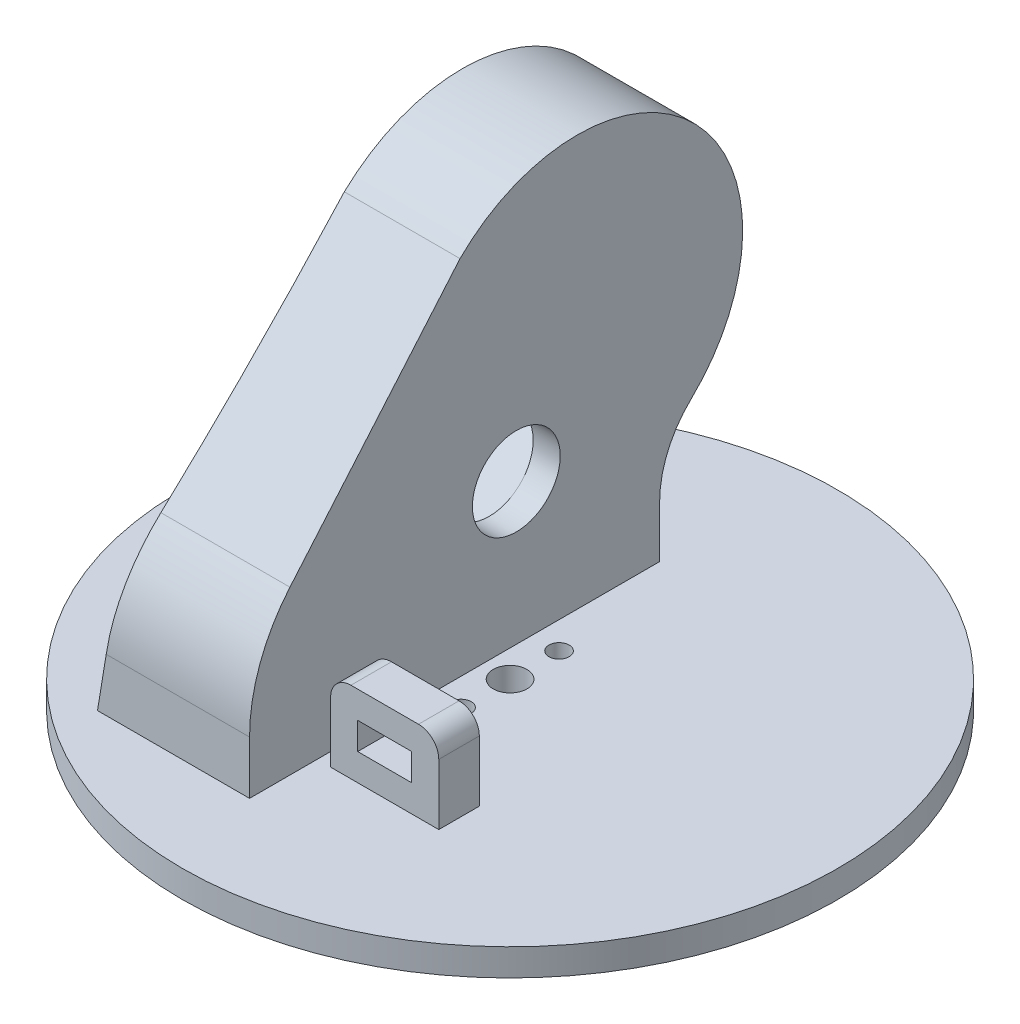
SolidWorks part; units mm, degrees
ref_plane "Front Plane" through (0, 0, 0) normal (0, 0, 1) x (1, 0, 0)
ref_plane "Top Plane" through (0, 0, 0) normal (0, 1, 0) x (1, 0, 0)
ref_plane "Right Plane" through (0, 0, 0) normal (1, 0, 0) x (0, 0, -1)
sketch "Sketch2" plane through (0, 0, 0) normal (0, 1, 0) x (1, 0, 0)
  circle A0 centre (0, 0) radius 48.5
  dimension "D1" = 97
extrude "Boss-Extrude1" add sketch "Sketch2" along normal blind 4
sketch "Sketch4" plane through (0, 0, 0) normal (0, -1, 0) x (1, 0, 0)
  circle A0 centre (0, 7.25) radius 1.5
  circle A1 centre (0, -7.25) radius 1.5
  dimension "D1" = 3
  dimension "D2" = 3
  dimension "D3" = 14.5
  dimension "D4" = 7.25
extrude "Cut-Extrude2" cut sketch "Sketch4" against normal through all
sketch "Sketch5" plane through (0, 0, 0) normal (0, -1, 0) x (1, 0, 0)
  circle A0 centre (0, 0) radius 2.5
  dimension "D1" = 5
extrude "Cut-Extrude3" cut sketch "Sketch5" against normal through all
ref_plane "Plane1" through (-4, 0, 0) normal (1, 0, 0) x (0, 0, -1)
sketch "Sketch7" plane through (-4, 0, 0) normal (1, 0, 0) x (0, 0, -1)
  line L0 (23.1299, 11.6445) -> (23.1299, 4)
  line L5 (48.5, 4) -> (-48.5, 4) construction
  line L6 (-27.2273, 29.5362) -> (-1.2843, 55.4793)
  line L7 (-43.5609, 4) -> (23.1299, 4)
  line L11 (-34.5496, 4) -> (-34.5496, 11.8586)
  arc A4 (28.7298, 24.692) -> (-1.2843, 55.4793) centre (13.9185, 40.2765) ccw
  arc A5 (28.7298, 24.692) -> (23.1299, 11.6445) centre (41.1299, 11.6445) ccw
  arc A6 (-27.2273, 29.5362) -> (-34.5496, 11.8586) centre (-9.5496, 11.8586) ccw
  dimension "D1" = 25
  dimension "D4" = 43
  dimension "D3" = 18
  dimension "D5" = 45
extrude "Boss-Extrude2" add sketch "Sketch7" against normal blind 14 contours A5 A4 L6 L7 L0 | A4 | A4 | A4 | L6 A6 L7 region at (-4, 29.3392, -2.7362)
ref_plane "Plane2" through (-6, 0, 0) normal (1, 0, 0) x (0, 0, -1)
sketch "Sketch17" plane through (-18, 0, 0) normal (-1, 0, 0) x (0, 0, 1)
  line L0 (29.3486, 31.6576) -> (3.4056, 57.6006)
  line L1 (-26.1299, 11.6445) -> (-26.1299, 1)
  line L2 (-26.1299, 1) -> (37.5496, 1)
  line L3 (37.5496, 1) -> (37.5496, 11.8586)
  line L4 (27.2273, 29.5362) -> (1.2843, 55.4793)
  line L5 (-23.1299, 11.6445) -> (-23.1299, 4)
  line L6 (-23.1299, 4) -> (34.5496, 4)
  line L7 (34.5496, 4) -> (34.5496, 11.8586)
  line L9 (-23.1299, 11.6445) -> (-23.1299, 4)
  line L10 (-23.1299, 4) -> (34.5496, 4)
  line L11 (34.5496, 4) -> (34.5496, 11.8586)
  line L12 (-26.1299, 4) -> (37.5496, 4)
  line L13 (48.5, 4) -> (-48.5, 4) construction
  line L14 (3.4056, 57.6006) -> (28.5745, 28.0776)
  line L15 (1.2843, 55.4793) -> (26.295, 26.1272)
  line L16 (31.5496, 11.8586) -> (31.5496, 4)
  line L18 (27.2273, 29.5362) -> (1.2843, 55.4793) construction
  arc A0 (3.4056, 57.6006) -> (-30.7965, 22.5174) centre (-13.9185, 40.2765) ccw
  arc A1 (-26.1299, 11.6445) -> (-30.7965, 22.5174) centre (-41.1299, 11.6445) ccw
  arc A2 (37.5496, 11.8586) -> (29.3486, 31.6576) centre (9.5496, 11.8586) ccw
  arc A3 (1.2843, 55.4793) -> (-28.7298, 24.692) centre (-13.9185, 40.2765) ccw
  arc A4 (-23.1299, 11.6445) -> (-28.7298, 24.692) centre (-41.1299, 11.6445) ccw
  arc A5 (34.5496, 11.8586) -> (27.2273, 29.5362) centre (9.5496, 11.8586) ccw
  arc A6 (1.2843, 55.4793) -> (-28.7298, 24.692) centre (-13.9185, 40.2765) ccw
  arc A7 (-23.1299, 11.6445) -> (-28.7298, 24.692) centre (-41.1299, 11.6445) ccw
  arc A8 (34.5496, 11.8586) -> (27.2273, 29.5362) centre (9.5496, 11.8586) ccw
  arc A9 (31.5496, 11.8586) -> (25.106, 27.4149) centre (9.5496, 11.8586) ccw
  line M16 (27.2273, 29.5362) -> (1.2843, 55.4793)
  arc M17 (1.2843, 55.4793) -> (-28.7298, 24.692) centre (-13.9185, 40.2765) ccw
  arc M18 (-28.7298, 24.692) -> (-23.1299, 11.6445) centre (-41.1299, 11.6445) cw
  line M19 (-23.1299, 11.6445) -> (-23.1299, 4)
  line M21 (34.5496, 4) -> (34.5496, 11.8586)
  arc M22 (34.5496, 11.8586) -> (27.2273, 29.5362) centre (9.5496, 11.8586) ccw
  dimension "D1" = 0
  dimension "D2" = 3
  dimension "D3" = 3
extrude "Boss-Extrude7" add sketch "Sketch17" along normal blind 9 and the other way up to surface (14 mm away) contours A9 L16 L12 L15 M21 M22 M16 | A1 L1 L12 L14 A0 M19 M18 M17 M16 M22 region at (-18, 42.2523, 15.3017) region at (-18, 20.289, 32.4332) other way up to face at (-4, 22.5305, 1.4471)
sketch "Sketch25" plane through (-18, 0, 0) normal (-1, 0, 0) x (0, 0, 1)
  line L0 (-23.1299, 11.6445) -> (-23.1299, 4)
  line L1 (48.5, 4) -> (-48.5, 4) construction
  line L2 (-23.1299, 11.6445) -> (-23.1299, 4) construction
  line L3 (1.2843, 55.4793) -> (26.295, 26.1272) construction
  line L4 (31.5496, 4) -> (-23.1299, 4) construction
  line L5 (31.5496, 11.8586) -> (31.5496, 4) construction
  line L6 (31.5496, 4) -> (-23.1299, 4)
  line L7 (31.5496, 11.8586) -> (31.5496, 4)
  line L8 (1.2843, 55.4793) -> (26.295, 26.1272)
  arc A0 (-23.1299, 11.6445) -> (-28.7298, 24.692) centre (-41.1299, 11.6445) ccw construction
  arc A1 (1.2843, 55.4793) -> (-28.7298, 24.692) centre (-13.9185, 40.2765) ccw construction
  arc A2 (-23.1299, 11.6445) -> (-28.7298, 24.692) centre (-41.1299, 11.6445) ccw
  arc A3 (31.5496, 11.8586) -> (26.295, 26.1272) centre (9.5496, 11.8586) ccw construction
  arc A4 (31.5496, 11.8586) -> (26.295, 26.1272) centre (9.5496, 11.8586) ccw
  spline S0 degree 3 poles (-28.7298, 24.692) (-21.9549, 18.2532) (-19.0941, 12.798) (-15.1299, 4) knots 0 0 0 0 1 1 1 1
  spline S1 degree 2 poles (11.7516, 43.195) (26.5513, 25.8264) (25.5496, 4) knots 0 0 0 1 1 1
  dimension "D2" = 8
  dimension "D1" = 6
extrude "Boss-Extrude10" add sketch "Sketch25" along normal up to surface (9 mm away) contours S0 L6 L0 A2 | A4 S1 A2 S0 L8 region at (-18, 9.918, -20.706) region at (-18, 17.2593, 26.6261) up to face at (-27, 22.2911, 0.3951)
sketch "Sketch26" plane through (0, 0, 0) normal (0, 0, 1) x (1, 0, 0)
  line L0 (-4, 64.7765) -> (-27, 64.7765) construction
  line L1 (-27, 4) -> (-4, 4) construction
  line L2 (-27, 4) -> (-27, 11.8586) construction
  line L3 (-26, 64.7765) -> (-27, 64.7765)
  line L4 (-27, 64.7765) -> (-27, 4)
  line L5 (-27, 4) -> (-23, 4)
  spline S0 degree 2 poles (-26, 64.7765) (-24.7724, 34.3751) (-23, 4) knots 0 0 0 1 1 1
  dimension "D1" = 1
  dimension "D2" = 4
  dimension "D3" = 2
extrude "Cut-Extrude15" [suppressed] cut sketch "Sketch26" against normal through all both and the other way through all contours L4 L5 S0 L3
sketch "Sketch27" plane through (0, 4, 0) normal (0, 1, 0) x (1, 0, 0)
  line L1 (-2, -18.5496) -> (14, -18.5496)
  line L2 (-2, -18.5496) -> (-2, -24.5496)
  line L3 (-2, -24.5496) -> (14, -24.5496)
  line L4 (14, -18.5496) -> (14, -24.5496)
  line L5 (-27, -34.5496) -> (-4, -34.5496) construction
  line L6 (-4, -34.5496) -> (-4, 26.1299) construction
  dimension "D1" = 10
  dimension "D2" = 6
  dimension "D3" = 16
  dimension "D4" = 2
extrude "Boss-Extrude11" add sketch "Sketch27" along normal blind 12
fillet "Fillet6" radius 3 2 edges at (14, 16, 21.5496) (-2, 16, 21.5496)
sketch "Sketch28" plane through (0, 0, 24.5496) normal (0, 0, 1) x (1, 0, 0)
  line L8 (10, 12) -> (2, 12)
  line L9 (2, 12) -> (2, 8)
  line L10 (2, 8) -> (10, 8)
  line L11 (10, 8) -> (10, 12)
  line L12 (10, 12) -> (2, 12)
  line L13 (2, 12) -> (2, 8)
  line L14 (2, 8) -> (10, 8)
  line L15 (10, 8) -> (10, 12)
  dimension "D1" = 4
extrude "Cut-Extrude16" cut sketch "Sketch28" against normal up to next
sketch "Sketch29" plane through (0, 0, 0) normal (0, 0, 1) x (1, 0, 0)
  line L0 (-4, 64.7765) -> (-27, 64.7765) construction
  line L1 (-27, 4) -> (-4, 4) construction
  line L2 (-21, 64.7765) -> (-27, 64.7765)
  line L3 (-27, 64.7765) -> (-27, 4)
  line L4 (-27, 4) -> (-26.5, 4)
  line L5 (48.5, 4) -> (-48.5, 4) construction
  spline S0 degree 2 poles (-21, 64.7765) (-21.2205, 34.1409) (-26.5, 4) knots 0 0 0 1 1 1
  dimension "D1" = 6
  dimension "D2" = 4
  dimension "D3" = 0.5
  dimension "D4" = 25
extrude "Cut-Extrude17" cut sketch "Sketch29" against normal through all both and the other way through all
sketch "Sketch31" plane through (-18, 0, 0) normal (-1, 0, 0) x (0, 0, 1)
  line L0 (-5.4155, 34.0546) -> (11.7496, 18.7458)
  line L1 (11.7496, 18.7458) -> (3.0968, 9.0438)
  line L2 (3.0968, 9.0438) -> (-14.0683, 24.3526)
  line L3 (-14.0683, 24.3526) -> (-5.4155, 34.0546)
  circle A0 centre (-4.9225, 24.9054) radius 6.5
  dimension "D1" = 6.5
extrude "Cut-Extrude18" cut sketch "Sketch31" against normal through all contours A0
extrude "Cut-Extrude19" cut sketch "Sketch31<3>" against normal blind 10 contours L0 L1 L2 L3
sketch "Sketch31<3>" plane through (-18, 0, 0) normal (-1, 0, 0) x (0, 0, 1) same geometry as "Sketch31"
sketch "Sketch32" plane through (-18, 0, 0) normal (-1, 0, 0) x (0, 0, 1)
  line L2 (3.1671, 26.4002) -> (-6.5457, 14.6527) construction
  line L3 (-5.4155, 34.0546) -> (11.7496, 18.7458) construction
  circle A0 centre (-11.5845, 30.655) radius 0.9205
  arc A4 (-9.2489, 29.7564) -> (-10.2349, 28.6509) centre (-4.9225, 24.9054) ccw construction
  circle A5 centre (10.1184, 12.7111) radius 0.9205
  dimension "D1" = 2.3
extrude "Cut-Extrude20" cut sketch "Sketch32" against normal blind 4 contours A0
extrude "Cut-Extrude21" cut sketch "Sketch32<3>" against normal blind 4
sketch "Sketch32<3>" plane through (-18, 0, 0) normal (-1, 0, 0) x (0, 0, 1) same geometry as "Sketch32"
